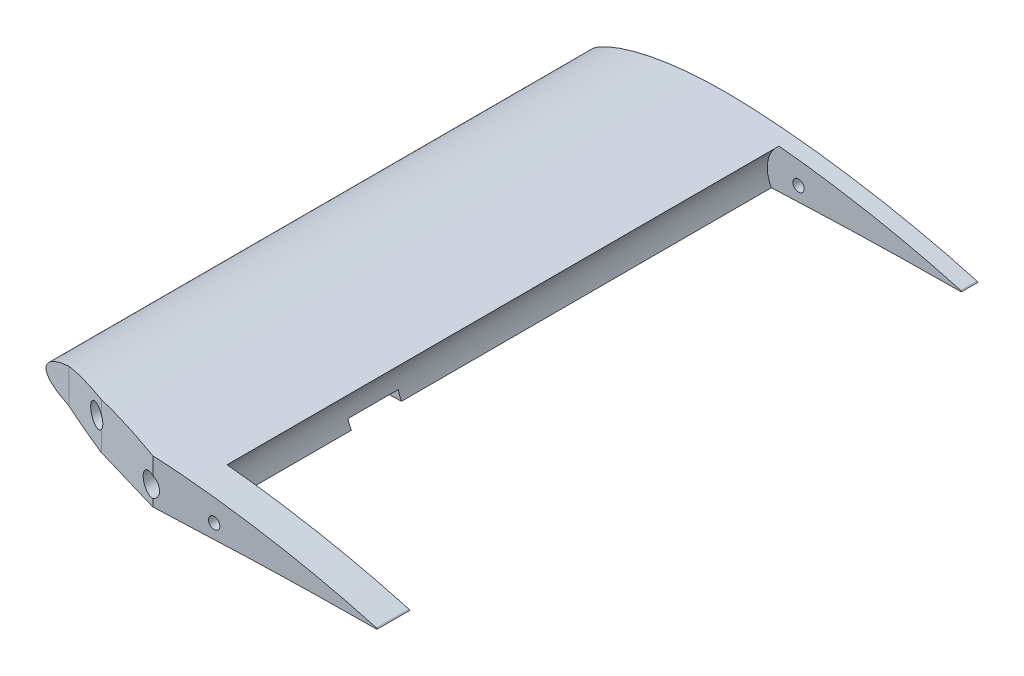
SolidWorks part; units mm, degrees
material "Balsa"
ref_plane "Front Plane" through (0, 0, 0) normal (0, 0, 1) x (1, 0, 0)
ref_plane "Top Plane" through (0, 0, 0) normal (0, 1, 0) x (1, 0, 0)
ref_plane "Right Plane" through (0, 0, 0) normal (1, 0, 0) x (0, 0, -1)
curve "曲線2"
  spline degree 3 poles (200, 0.26, 0) (196.6701, 1.1665, 0) (190.0264, 2.975, 0) (176.7171, 6.2635, 0) (160.0733, 9.8968, 0) (140.0541, 13.4784, 0) (120.0503, 16.4141, 0) (100.0354, 18.5082, 0) (80.0223, 19.8143, 0) (63.3151, 19.8275, 0) (49.9753, 18.9046, 0) (39.957, 17.689, 0) (29.917, 15.8963, 0) (21.5972, 13.7404, 0) (14.9301, 11.563, 0) (9.903, 9.5074, 0) (5.6136, 7.2843, 0) (1.8903, 4.6252, 0) (-1.3508, 0.3484, 0) (2.1476, -2.9224, 0) (5.7173, -4.2063, 0) (9.9686, -5.0729, 0) (14.9893, -5.5135, 0) (21.6639, -5.8253, 0) (30.0021, -5.8019, 0) (40.0043, -5.522, 0) (49.9995, -4.9891, 0) (63.3329, -4.3655, 0) (79.9968, -3.5653, 0) (100.0006, -2.8138, 0) (119.9979, -1.9794, 0) (139.9972, -1.2688, 0) (159.998, -0.746, 0) (176.6662, -0.4806, 0) (189.9997, -0.3058, 0) (196.6666, -0.2753, 0) (200, -0.26, 0) knots 0 0 0 0 0.025305 0.050488 0.10052 0.150191 0.199587 0.24874 0.297716 0.346601 0.371103 0.395726 0.42057 0.445825 0.458702 0.47192 0.485786 0.493461 0.506863 0.516148 0.522766 0.535269 0.547551 0.559786 0.584229 0.608681 0.633151 0.657622 0.706558 0.755482 0.804406 0.85332 0.902221 0.951113 0.975557 1 1 1 1
sketch "草圖4" plane through (0, 0, 0) normal (0, 0, 1) x (1, 0, 0)
  line L8 (26.3929, -5.7959) -> (118.9885, -5.7959) construction
  spline S1 degree 2 poles (120, 0.156) (120.5501, 0) (120, -0.156) knots 0 0 0 1 1 1
  spline S2 degree 3 poles (120, 0.156) (118.0021, 0.6999) (114.0158, 1.785) (106.0302, 3.7581) (96.044, 5.9381) (84.0324, 8.087) (72.0302, 9.8485) (60.0213, 11.1049) (48.0134, 11.8886) (37.9891, 11.8965) (29.9852, 11.3428) (23.9742, 10.6134) (17.9502, 9.5378) (12.9583, 8.2442) (8.9581, 6.9378) (5.9418, 5.7044) (3.3681, 4.3706) (1.1342, 2.7751) (-0.8105, 0.209) (1.2885, -1.7534) (3.4304, -2.5238) (5.9811, -3.0437) (8.9936, -3.3081) (12.9983, -3.4952) (18.0013, -3.4812) (24.0026, -3.3132) (29.9997, -2.9935) (37.9998, -2.6193) (47.9981, -2.1392) (60.0003, -1.6883) (71.9988, -1.1877) (83.9983, -0.7613) (95.9988, -0.4476) (105.9997, -0.2883) (113.9998, -0.1835) (118, -0.1652) (120, -0.156) knots 0 0 0 0 0.025305 0.050488 0.10052 0.150191 0.199587 0.24874 0.297716 0.346601 0.371103 0.395726 0.42057 0.445825 0.458702 0.47192 0.485786 0.493461 0.506863 0.516148 0.522766 0.535269 0.547551 0.559786 0.584229 0.608681 0.633151 0.657622 0.706558 0.755482 0.804406 0.85332 0.902221 0.951113 0.975557 1 1 1 1
extrude "填料-伸長1" add sketch "草圖4" along normal blind 185
sketch "草圖2" plane through (0, 0, 0) normal (0, 0, -1) x (-1, 0, 0)
  line L0 (-49.9391, 3.2561) -> (-25, 5) construction
  line L1 (-31.2982, 15.2311) -> (-54.8503, 15.2311) construction
  circle A0 centre (-25, 5) radius 3.25
  circle A1 centre (-49.9391, 3.2561) radius 3.25
  dimension "D1" = 6.5
  dimension "D2" = 25
  dimension "D3" = 25
  dimension "D4" = 5
  dimension "D5" = 356
extrude "除料-伸長1" cut sketch "草圖2" against normal through all
sketch "草圖3" plane through (0, 0, 0) normal (0, 1, 0) x (1, 0, 0)
  line L0 (120, 0) -> (-0.0337, 0) construction
  line L1 (70.275, -10) -> (120.275, -10)
  line L2 (70.275, -10) -> (70.275, -180)
  line L3 (70.275, -180) -> (120.275, -180)
  line L4 (120.275, -10) -> (120.275, -180)
  line L6 (-0.0337, -185) -> (120, -185) construction
  line L7 (51.1104, 0) -> (27.6363, -7.6409)
  line L8 (27.6363, -7.6409) -> (9.8855, -15.3784)
  line L9 (9.8855, -15.3784) -> (-0.0337, -18.2322)
  line L10 (-0.0337, 0) -> (-0.0337, -185) construction
  line L11 (-0.0337, -18.2322) -> (-0.0337, 0)
  line L12 (-0.0337, 0) -> (51.1104, 0)
  dimension "D1" = 10
  dimension "D2" = 50
  dimension "D3" = 5
extrude "除料-伸長2" cut sketch "草圖3" against normal through all and the other way through all
sketch "草圖5" plane through (0, 0, 0) normal (0, 0, -1) x (-1, 0, 0)
  circle A0 centre (-70, 3.156) radius 1.75
  dimension "D3" = 3.5
  dimension "D1" = 50
  dimension "D2" = 3
extrude "除料-伸長3" cut sketch "草圖5" against normal through all
sketch "草圖6" plane through (0, 0, 0) normal (0, 0, -1) x (-1, 0, 0)
  circle A0 centre (-70, 3.156) radius 9.6299
extrude "除料-伸長4" cut sketch "草圖6" against normal up to surface (180 mm away) from surface up to face at (87.0958, 1.5668, 180) starting at face at (87.0958, 3.4412, 10)
sketch "草圖7" plane through (0, 0, 0) normal (0, 1, 0) x (1, 0, 0)
  line L0 (51.6349, -66.0861) -> (82.522, -66.0861)
  line L6 (51.6349, -50.6158) -> (82.522, -50.6158)
  line L7 (8.4126, -66.0861) -> (17.6349, -66.0861)
  line L8 (8.4126, -66.0861) -> (8.4126, -50.6158)
  line L9 (8.4126, -50.6158) -> (17.6349, -50.6158)
  line L10 (82.522, -66.0861) -> (82.522, -50.6158)
  line L11 (17.6349, -50.6158) -> (51.6349, -50.6158)
  line L13 (17.6349, -66.0861) -> (17.6349, -91.0861)
  line L14 (17.6349, -91.0861) -> (51.6349, -91.0861)
  line L15 (51.6349, -66.0861) -> (51.6349, -91.0861)
  dimension "D1" = 25
extrude "除料-伸長5" cut sketch "草圖7" against normal through all and the other way blind 1
mirror "鏡射1" about plane through (0.3692, 1.5728, 0) normal (0, 0, -1) of bodies 174
sketch "草圖8" plane through (0, 0, 0) normal (0, 1, 0) x (1, 0, 0)
  line L1 (230.0413, 0) -> (-216.3527, 0)
  line L2 (230.0413, 0) -> (230.0413, -202.8182)
  line L3 (230.0413, -202.8182) -> (-216.3527, -202.8182)
  line L4 (-216.3527, 0) -> (-216.3527, -202.8182)
extrude "除料-伸長7" cut sketch "草圖8" against normal through all and the other way through all
